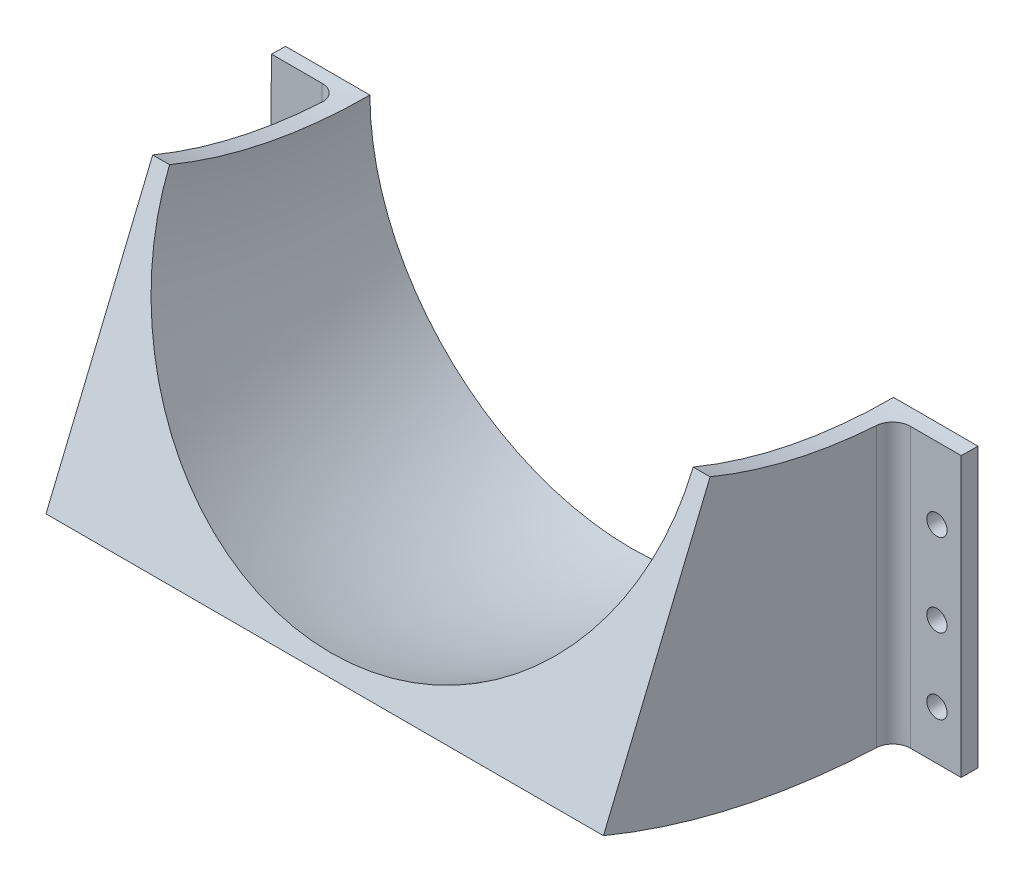
SolidWorks part; units mm, degrees
ref_plane "Front Plane" through (0, 0, 0) normal (0, 0, 1) x (1, 0, 0)
ref_plane "Top Plane" through (0, 0, 0) normal (0, 1, 0) x (1, 0, 0)
ref_plane "Right Plane" through (0, 0, 0) normal (1, 0, 0) x (0, 0, -1)
sketch "Sketch9" plane through (0, 0, 0) normal (0, 0, 1) x (1, 0, 0)
  line L0 (-49.2252, -98.425) -> (-52.4002, -98.425)
  line L1 (-52.4002, -115.251) -> (-52.4002, -77.9954) construction
  line L2 (-65.1002, -98.425) -> (-52.4002, -98.425) construction
  line L3 (49.2252, -98.425) -> (52.4002, -98.425)
  line L4 (52.4002, -98.425) -> (52.4002, -150.8252)
  line L5 (-52.4002, -98.425) -> (-52.4002, -150.8252)
  line L6 (-52.4002, -150.8252) -> (52.4002, -150.8252)
  arc A0 (-49.2252, -98.425) -> (49.2252, -98.425) centre (0, -98.425) ccw construction
  arc A1 (-49.2252, -98.425) -> (49.2252, -98.425) centre (0, -98.425) ccw
ref_axis "Axis2" through (-38.0489, 0, 0) along (1, 0, 0)
revolve "Revolve8" add sketch "Sketch9" angle 22.5 about axis through (-38.0489, 0, 0) along (1, 0, 0) other way angle 22.5 reverse direction yes
sketch "Sketch10" plane through (52.4002, 0, 0) normal (1, 0, 0) x (0, 0, -1)
  line L0 (0, -98.425) -> (0, -150.8252)
  line L1 (0, -150.8252) -> (-3.1748, -150.7918)
  line L2 (-3.1748, -150.7918) -> (-3.1748, -98.3738)
  arc A0 (-57.7183, -139.3443) -> (0, -150.8252) centre (0, 0) ccw construction
  arc A1 (-37.6656, -90.9328) -> (0, -98.425) centre (0, 0) ccw construction
  arc A2 (-3.1748, -98.3738) -> (0, -98.425) centre (0, 0) ccw
  dimension "D1" = 3.175
sketch "Sketch11" plane through (-52.4002, 0, 0) normal (-1, 0, 0) x (0, 0, 1)
  line L0 (0, -98.425) -> (0, -150.8252)
  line L2 (3.1748, -150.7918) -> (2.6232, -98.39)
  arc A0 (0, -150.8252) -> (57.7183, -139.3443) centre (0, 0) ccw construction
  arc A2 (0, -98.425) -> (37.6656, -90.9328) centre (0, 0) ccw construction
  arc A3 (0, -98.425) -> (2.6232, -98.39) centre (0, 0) ccw
  arc A4 (0, -150.8252) -> (3.1748, -150.7918) centre (0, 0) ccw
  dimension "D1" = 3.175
extrude "Boss-Extrude3" add sketch "Sketch11" along normal blind 12.7
extrude "Boss-Extrude4" add sketch "Sketch10" along normal blind 12.7
sketch "Sketch12" plane through (0, 0, 3.1748) normal (0, 0, 1) x (1, 0, 0)
  circle A1 centre (60.5502, -111.886) radius 1.905
  circle A2 centre (60.5502, -111.886) radius 1.905
  circle A3 centre (60.5502, -141.5668) radius 1.905
  circle A4 centre (60.5502, -141.5668) radius 1.905
  circle A5 centre (60.5502, -127.4445) radius 1.905
  circle A6 centre (60.5502, -127.4445) radius 1.905
  dimension "D1" = 0
  dimension "D2" = 0
  dimension "D3" = 0
extrude "Cut-Extrude4" cut sketch "Sketch12" against normal blind 3.175
sketch "Sketch13" plane through (0, -0.0084, 1.5877) normal (0, 0.0105, 0.9999) x (1, 0, 0)
  circle A1 centre (-60.754, -141.5219) radius 1.905
  circle A2 centre (-60.754, -141.5219) radius 1.905
  circle A3 centre (-60.754, -112.4795) radius 1.905
  circle A4 centre (-60.754, -112.4795) radius 1.905
  circle A5 centre (-60.754, -127.4445) radius 1.905
  circle A6 centre (-60.754, -127.4445) radius 1.905
  dimension "D1" = 0
  dimension "D2" = 0
  dimension "D3" = 0
extrude "Cut-Extrude5" cut sketch "Sketch13" against normal blind 3.175
fillet "Flange Reinforcement" radius 3.175 2 edges
